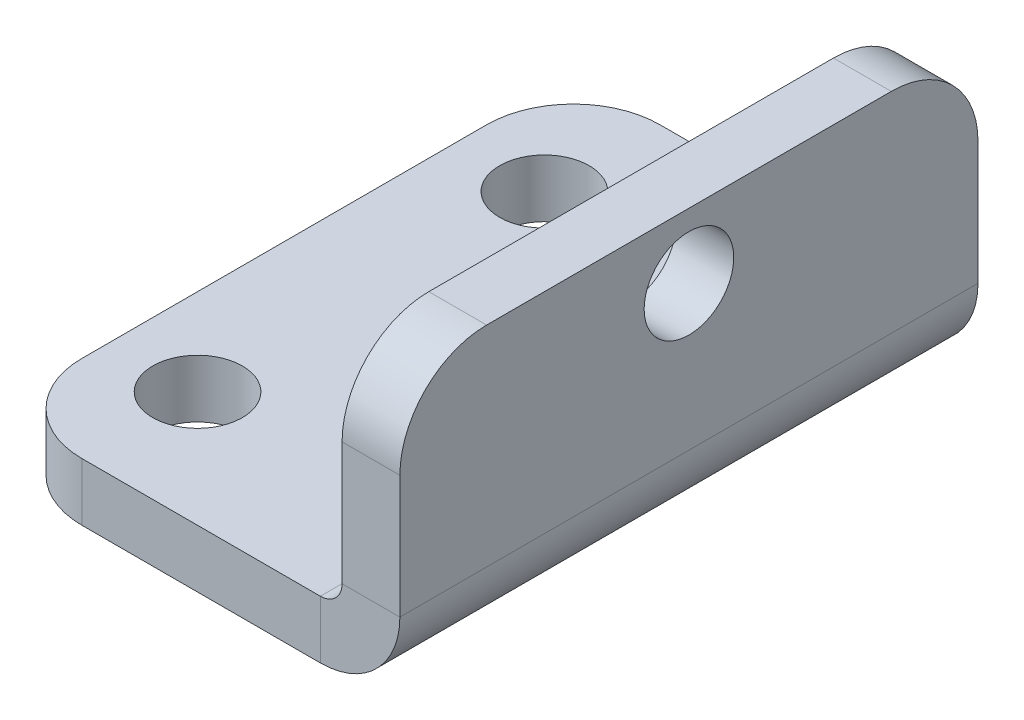
SolidWorks part; units mm, degrees
note: The reader was unsure of these and kept them because the rebuilt part matched: bend radius of "BaseBend1".
ref_plane "Front Plane" through (0, 0, 0) normal (0, 0, 1) x (1, 0, 0)
ref_plane "Top Plane" through (0, 0, 0) normal (0, 1, 0) x (1, 0, 0)
ref_plane "Right Plane" through (0, 0, 0) normal (1, 0, 0) x (0, 0, -1)
sketch "Sketch1" plane through (0, 0, 0) normal (0, 0, 1) x (1, 0, 0)
  line L0 (-12, 0) -> (0, 0)
  line L1 (0, 0) -> (0, 8)
  dimension "D1" = 12
  dimension "D2" = 8
base flange "Base-Flange1" sketch "Sketch1" end condition mid plane depth 20 reverse direction no thickness 2 reverse thickness direction no bend radius 0.75
bend "BaseBend1" bend radius 0.75 bend angle 90 parameters "D5"=1
fillet "Fillet1" radius 3 4 edges at (-12, -1, 10) (-12, -1, -10) (1, 8, -10) (1, 8, 10)
sketch "Sketch6" plane through (0, 0, 0) normal (0, 1, 0) x (1, 0, 0)
  line L0 (-12, -7) -> (-12, 7) construction
  line L1 (0, 0) -> (-12, 0) construction
  line L2 (-12, 0) -> (0, 0) construction
  circle A0 centre (-9, 6) radius 1.55
  circle A1 centre (-9, -6) radius 1.55
  dimension "D1" = 3
  dimension "D2" = 3.1
  dimension "D3" = 6
extrude "Cut-Extrude1" cut sketch "Sketch6" against normal through all normal cut yes
sketch "Sketch7" plane through (0, 0, 0) normal (-1, 0, 0) x (0, 0, 1)
  line L0 (0, 0) -> (0, 8) construction
  circle A0 centre (0, 5.75) radius 1.55
  circle A1 centre (0, 5.75) radius 0.75 construction
  dimension "D1" = 3.1
extrude "Cut-Extrude2" cut sketch "Sketch7" against normal through all normal cut yes
sketch "Bend-Lines1" [suppressed] plane through (0, 0, 0) normal (0, 1, 0) x (1, 0, 0)
sketch "Bounding-Box1" [suppressed] plane through (0, 0, 0) normal (0, 1, 0) x (1, 0, 0)
sheet metal parameters "Sheet-Metal1" thickness 2 parameters "D1"=0.75
flat pattern "Flat-Pattern1" [suppressed]
sketch "Bend-Lines2" plane through (0, 0, 0) normal (0, 1, 0) x (1, 0, 0)
  line L0 (0.436, 10) -> (0.436, -10) construction
  line L1 (0.436, 10) -> (0.436, -10) construction
sketch3d "Bounding-Box2" [suppressed]
  line L0 (0, 0, 0) -> (20.8719, 0, 0) construction
  line L1 (0, 20, 0) -> (20.8719, 20, 0) construction
  line L2 (0, 0, 0) -> (0, 20, 0) construction
  line L3 (20.8719, 0, 0) -> (20.8719, 20, 0) construction
bend of the flat pattern "Flatten-<BaseBend1>1"
sheet metal parameters "Sheet-Metal2" thickness 2 parameters "D1"=0.75
flat pattern "Flat-Pattern1"
sketch "Bend-Lines2" plane through (0, 0, 0) normal (0, 1, 0) x (1, 0, 0)
  line L0 (0.436, 10) -> (0.436, -10) construction
  line L1 (0.436, 10) -> (0.436, -10) construction
sketch3d "Bounding-Box2" [suppressed]
  line L0 (0, 0, 0) -> (20.8719, 0, 0) construction
  line L1 (0, 20, 0) -> (20.8719, 20, 0) construction
  line L2 (0, 0, 0) -> (0, 20, 0) construction
  line L3 (20.8719, 0, 0) -> (20.8719, 20, 0) construction
bend of the flat pattern "Flatten-<BaseBend1>1"
sheet metal parameters "Sheet-Metal3" thickness 2 parameters "D1"=0.75
flat pattern "Flat-Pattern1"
sketch "Bend-Lines2" plane through (0, 0, 0) normal (0, 1, 0) x (1, 0, 0)
  line L0 (0.436, 10) -> (0.436, -10) construction
  line L1 (0.436, 10) -> (0.436, -10) construction
sketch3d "Bounding-Box2" [suppressed]
  line L0 (0, 0, 0) -> (20.8719, 0, 0) construction
  line L1 (0, 20, 0) -> (20.8719, 20, 0) construction
  line L2 (0, 0, 0) -> (0, 20, 0) construction
  line L3 (20.8719, 0, 0) -> (20.8719, 20, 0) construction
bend of the flat pattern "Flatten-<BaseBend1>1"
